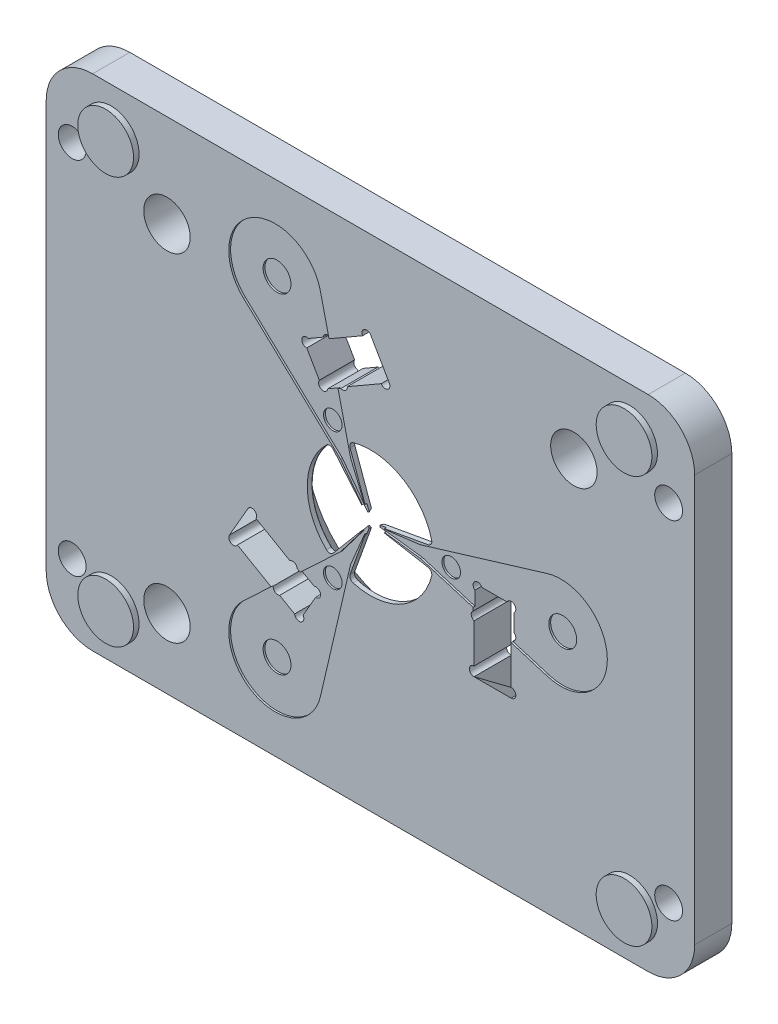
SolidWorks part; units mm, degrees
ref_plane "前基準面" through (0, 0, 0) normal (0, 0, 1) x (1, 0, 0)
ref_plane "上基準面" through (0, 0, 0) normal (0, 1, 0) x (1, 0, 0)
ref_plane "右基準面" through (0, 0, 0) normal (1, 0, 0) x (0, 0, -1)
sketch "草圖1" plane through (0, 0, 0) normal (0, 0, 1) x (1, 0, 0)
  line L1 (-38, 30) -> (38, 30)
  line L2 (-38, 30) -> (-38, -30)
  line L3 (-38, -30) -> (38, -30)
  line L4 (38, 30) -> (38, -30)
  line L5 (-38, 30) -> (38, -30) construction
  line L6 (-38, -30) -> (38, 30) construction
  point P0 (0, 0)
  point P28 (0, 0)
  dimension "D1" = 76
  dimension "D2" = 60
extrude "填料-伸長1" add sketch "草圖1" along normal blind 4
sketch "草圖2" plane through (0, 0, 4) normal (0, 0, 1) x (1, 0, 0)
  line L6 (0.3574, 0.005) -> (20.1903, 2.4807) construction
  line L7 (0.3574, -0.005) -> (20.1903, -2.4807) construction
  line L8 (0.3574, 0.005) -> (4.5094, 0.5233)
  line L9 (0.3574, -0.005) -> (4.5094, -0.5233)
  line L10 (6.1751, 0.8773) -> (19.0478, 4.7845)
  line L11 (6.1751, -0.8773) -> (19.0478, -4.7845)
  line L12 (-2.3278, -5.7864) -> (-5.3804, -18.8881)
  line L13 (-0.1744, -0.312) -> (-1.8015, -4.1669)
  line L14 (-0.183, -0.307) -> (-2.7079, -3.6436)
  line L15 (-3.8473, -4.9091) -> (-13.6674, -14.1037)
  line L16 (-3.8473, 4.9091) -> (-13.6674, 14.1037)
  line L17 (-0.183, 0.307) -> (-2.7079, 3.6436)
  line L18 (-0.1744, 0.312) -> (-1.8015, 4.1669)
  line L19 (-2.3278, 5.7864) -> (-5.3804, 18.8881)
  circle A7 centre (0, 0) radius 0.353 construction
  arc A8 (0.3574, 0.005) -> (0.3574, -0.005) centre (0.358, 0) ccw
  arc A9 (19.0478, -4.7845) -> (19.0478, 4.7845) centre (20.5, 0) ccw
  circle A10 centre (20.5, 0) radius 2.5 construction
  arc A11 (4.5094, -0.5233) -> (6.1751, -0.8773) centre (3.2707, -10.4463) cw
  arc A12 (4.5094, 0.5233) -> (6.1751, 0.8773) centre (3.2707, 10.4463) ccw
  arc A13 (-13.6674, -14.1037) -> (-5.3804, -18.8881) centre (-10.25, -17.7535) ccw
  arc A14 (-1.8015, -4.1669) -> (-2.3278, -5.7864) centre (7.4114, -8.0556) ccw
  arc A15 (-0.1744, -0.312) -> (-0.183, -0.307) centre (-0.179, -0.31) ccw
  arc A16 (-2.7079, -3.6436) -> (-3.8473, -4.9091) centre (-10.6821, 2.3906) cw
  arc A17 (-5.3804, 18.8881) -> (-13.6674, 14.1037) centre (-10.25, 17.7535) ccw
  arc A18 (-2.7079, 3.6436) -> (-3.8473, 4.9091) centre (-10.6821, -2.3906) ccw
  arc A19 (-0.183, 0.307) -> (-0.1744, 0.312) centre (-0.179, 0.31) ccw
  arc A20 (-1.8015, 4.1669) -> (-2.3278, 5.7864) centre (7.4114, 8.0556) cw
  point P17 (5.3574, -0.6291)
  point P20 (5.3574, 0.6291)
  point P46 (0, 0)
  dimension "D1" = 0.706
  dimension "D2" = 0.01
  dimension "D3" = 10
  dimension "D6" = 5
  dimension "D4" = 5
  dimension "D7" = 10
  dimension "D9" = 0.6201
  dimension "D5" = 20.5
  dimension "D8" = 3
extrude "除料-伸長1" cut sketch "草圖2" against normal blind 0.5
sketch "草圖5" plane through (0, 0, 4) normal (0, 0, 1) x (1, 0, 0)
  line L0 (-29.9, 26.9) -> (29.9, 26.9)
  line L1 (-38, 30) -> (-38, -30) construction
  line L2 (38, -30) -> (38, 30) construction
  line L3 (34.9, 21.9) -> (34.9, -21.9)
  line L4 (38, 30) -> (-38, 30) construction
  line L5 (-38, -30) -> (38, -30) construction
  line L6 (-29.9, -26.9) -> (29.9, -26.9)
  line L7 (-34.9, 21.9) -> (-34.9, -21.9)
  arc A0 (-29.9, -26.9) -> (-34.9, -21.9) centre (-29.9, -21.9) cw
  arc A1 (34.9, -21.9) -> (29.9, -26.9) centre (29.9, -21.9) cw
  arc A2 (29.9, 26.9) -> (34.9, 21.9) centre (29.9, 21.9) cw
  arc A3 (-34.9, 21.9) -> (-29.9, 26.9) centre (-29.9, 21.9) cw
  line M29 (38, -30) -> (38, 30)
  line M30 (38, 30) -> (-38, 30)
  line M31 (-38, 30) -> (-38, -30)
  line M32 (-38, -30) -> (38, -30)
  dimension "D5" = 5
  dimension "D1" = 3.1
  dimension "D2" = 3.1
  dimension "D3" = 3.1
  dimension "D4" = 3.1
extrude "除料-伸長4" cut sketch "草圖5" against normal blind 10 contours L7 A3 L0 A2 L3 A1 L6 A0 M32 M29 M30 M31 region at (0, -29.0317, 4)
ref_plane "平面1" through (0, 0, 4) normal (0, 0, 1) x (1, 0, 0)
sketch "草圖7" plane through (0, 0, 4) normal (0, 0, 1) x (1, 0, 0)
  line L0 (0, 0) -> (34.9, 0) construction
  line L1 (34.9, 21.9) -> (34.9, -21.9) construction
  line L2 (11.05, -0.2286) -> (15.25, -0.2286)
  line L3 (15.25, -0.2286) -> (15.25, -3.3286)
  line L4 (15.25, -3.3286) -> (11.05, -3.3286)
  line L5 (11.05, -3.3286) -> (11.05, -0.2286)
  line L6 (11.05, -1.7786) -> (15.25, -1.7786) construction
  line L7 (13.15, -0.2286) -> (13.15, -3.3286) construction
  line L8 (13.15, -1.7786) -> (11.05, -0.2286) construction
  line L9 (0, 0) -> (-12.75, -22.0836) construction
  line L10 (-6.575, -11.3882) -> (-6.9709, -11.1597) construction
  line L11 (-5.7229, -9.4553) -> (-7.8229, -13.0926)
  line L16 (-7.4271, 13.3212) -> (-5.3271, 9.6839)
  line L17 (-7.4271, 13.3212) -> (-4.7424, 14.8712)
  line L18 (-4.7424, 14.8712) -> (-2.6424, 11.2339)
  line L23 (13.15, -1.7786) -> (13.15, -13.7786) construction
  line L24 (11.15, -7.7786) -> (15.15, -7.7786)
  line L25 (11.15, -7.7786) -> (11.15, -8.7786)
  line L26 (11.15, -8.7786) -> (15.15, -8.7786)
  line L27 (15.15, -8.7786) -> (15.15, -7.7786)
  line L28 (-2.6424, 11.2339) -> (-5.3271, 9.6839)
  line L33 (-6.0847, 14.0962) -> (-3.9847, 10.4589) construction
  line L34 (11.15, -8.2786) -> (15.15, -8.2786) construction
  line L35 (-5.7229, -9.4553) -> (-8.4076, -7.9053)
  line L40 (-8.4076, -7.9053) -> (-10.5076, -11.5426)
  line L41 (0, 0) -> (-12.75, 22.0836) construction
  line L42 (-6.575, 11.3882) -> (-6.1791, 11.6168) construction
  line L43 (-6.3771, 11.5025) -> (-3.6924, 13.0525) construction
  line L44 (-10.5076, -11.5426) -> (-7.8229, -13.0926)
  line L45 (-7.0653, -8.6803) -> (-9.1653, -12.3176) construction
  line L46 (-9.4576, -9.7239) -> (-6.7729, -11.2739) construction
  line L47 (-8.4076, -7.9053) -> (-7.8229, -13.0926) construction
  line L48 (-10.5076, -11.5426) -> (-5.7229, -9.4553) construction
  line L49 (-9.4576, -9.7239) -> (-17.1653, -5.2739) construction
  line L50 (-12.3114, -5.7669) -> (-14.3114, -9.231)
  line L51 (-4.7424, 14.8712) -> (-5.3271, 9.6839) construction
  line L52 (-7.4271, 13.3212) -> (-2.6424, 11.2339) construction
  line L53 (-3.6924, 13.0525) -> (4.0153, 17.5025) construction
  line L54 (-0.8386, 17.0096) -> (1.1614, 13.5455)
  line L55 (-0.8386, 17.0096) -> (0.0275, 17.5096)
  line L56 (0.0275, 17.5096) -> (2.0275, 14.0455)
  line L57 (2.0275, 14.0455) -> (1.1614, 13.5455)
  line L58 (-0.4055, 17.2596) -> (1.5945, 13.7955) construction
  line L59 (-4.3091, 13.6779) -> (-3.8841, 12.9418) construction
  line L60 (-4.7841, 14.5007) -> (-4.3091, 13.6779) construction
  line L61 (-12.3114, -5.7669) -> (-13.1775, -5.2669)
  line L62 (-13.1775, -5.2669) -> (-15.1775, -8.731)
  line L63 (-15.1775, -8.731) -> (-14.3114, -9.231)
  line L64 (-12.7445, -5.5169) -> (-14.7445, -8.981) construction
  line L65 (-10.1659, -11.3935) -> (-9.6909, -10.5708) construction
  line L66 (-9.6909, -10.5708) -> (-9.2659, -9.8347) construction
  circle A0 centre (11.35, -0.45) radius 0.5
  circle A1 centre (14.95, -0.45) radius 0.5
  circle A2 centre (14.95, -3.1071) radius 0.5
  circle A3 centre (11.35, -3.1071) radius 0.5
  circle A4 centre (13.15, -0.9886) radius 0.15 construction
  arc A11 (-13.6674, -14.1037) -> (-5.3804, -18.8881) centre (-10.25, -17.7535) ccw construction
  circle A17 centre (-7.0853, 13.1721) radius 0.5
  circle A20 centre (15.15, -8.2786) radius 0.5
  circle A21 centre (11.15, -8.2786) radius 0.5
  arc A24 (-5.3804, 18.8881) -> (-13.6674, 14.1037) centre (-10.25, 17.7535) ccw construction
  circle A25 centre (-7.8647, -12.7221) radius 0.5
  circle A26 centre (-10.1659, -11.3935) radius 0.5
  circle A27 centre (-6.0647, -9.6044) radius 0.5
  circle A28 centre (-8.3659, -8.2758) radius 0.5
  circle A29 centre (-14.7445, -8.981) radius 0.5
  circle A30 centre (-12.7445, -5.5169) radius 0.5
  circle A31 centre (-4.7841, 14.5007) radius 0.5
  circle A32 centre (-2.9841, 11.383) radius 0.5
  circle A33 centre (-5.2853, 10.0544) radius 0.5
  circle A34 centre (-0.4055, 17.2596) radius 0.5
  circle A35 centre (1.5945, 13.7955) radius 0.5
  point P24 (13.15, -7.7786)
  point P37 (-6.7729, -11.2739)
  point P52 (-6.3771, 11.5025)
  point P70 (0.1614, 15.2775)
  point P89 (-13.3114, -7.4989)
  dimension "D3" = 1
  dimension "D4" = 0.3
  dimension "D10" = 13.15
  dimension "D23" = 0.3
  dimension "D17" = 1
  dimension "D24" = 0.45
  dimension "D25" = 4
  dimension "D30" = 0.45
  dimension "D20" = 1
  dimension "D1" = 4.2
  dimension "D2" = 3.1
  dimension "D5" = 0.79
  dimension "D6" = 0.45
  dimension "D7" = 13.15
  dimension "D11" = 13.15
  dimension "D12" = 4.2
  dimension "D13" = 4
  dimension "D14" = 1
  dimension "D15" = 4.2
  dimension "D16" = 3.1
  dimension "D18" = 4.95
  dimension "D19" = 3.1
  dimension "D21" = 0.3
  dimension "D22" = 0.3
  dimension "D26" = 1
  dimension "D27" = 4.95
  dimension "D29" = 1.25
  dimension "D31" = 4
  dimension "D32" = 1
  dimension "D33" = 4.95
  dimension "D35" = 1.25
extrude "除料-伸長5" cut sketch "草圖7" against normal through all contours A2 L3 A1 L2 A0 L5 A3 L4 | A25 A27 | A17 L17 | A35 L56 A34 L54 | A28 L40 A26 L44 A25 L11 A27 L35 | A30 L62 A29 L50 | A2 | A1 | A0 | A3 | A27 | A25 | A17 | L24 L27 L26 L25 | A20 | A21 | A33 | A32 | A31 | A34 | A35 | A26 | A28 | A29 | A30 region at (13.15, -1.7786, 4) region at (-6.1957, -9.613, 4) region at (-8.1153, -10.4989, 4) region at (-5.0347, 12.2775, 4) region at (-13.7445, -7.2489, 4) region at (0.5945, 15.5275, 4)
sketch "草圖9" plane through (0, 0, 4) normal (0, 0, 1) x (1, 0, 0)
  line L0 (34.9, 21.9) -> (24.9, 21.9) construction
  line L1 (24.9, 21.9) -> (24.9, -21.9) construction
  line L2 (24.9, -21.9) -> (34.9, -21.9) construction
  line L3 (34.9, 21.9) -> (34.9, -21.9) construction
  line L4 (0, 26.9) -> (0, -26.9) construction
  line L5 (-29.9, 26.9) -> (29.9, 26.9) construction
  line L6 (-29.9, -26.9) -> (29.9, -26.9) construction
  line L7 (34.9, 0) -> (-34.9, 0) construction
  line L8 (-34.9, 21.9) -> (-34.9, -21.9) construction
  circle A0 centre (32.1, 17.9) radius 1.5
  circle A3 centre (-32.1, 19.4) radius 1.5
  circle A4 centre (-32.1, -19.4) radius 1.5
  circle A5 centre (32.1, -19.4) radius 1.5
  dimension "D2" = 3
  dimension "D5" = 2.8
  dimension "D3" = 3
  dimension "D7" = 2.8
  dimension "D1" = 10
  dimension "D4" = 4
  dimension "D6" = 2.5
extrude "除料-伸長6" cut sketch "草圖9" against normal through all
sketch "草圖13" plane through (0, 0, 4) normal (0, 0, 1) x (1, 0, 0)
  line L0 (5.358, 0.6292) -> (19.0478, 4.7845) construction
  line L1 (0.3574, 0.005) -> (20.1903, 2.4807) construction
  line L2 (20.1903, -2.4807) -> (0.3574, -0.005) construction
  line L15 (0.3574, 0.005) -> (5.358, 0.6292) construction
  line L16 (0.3574, -0.005) -> (5.358, -0.6292) construction
  line L17 (5.358, -0.6292) -> (19.0478, -4.7845) construction
  line L18 (-2.1341, -4.9548) -> (-5.3804, -18.8881) construction
  line L19 (-0.1744, -0.312) -> (-2.1341, -4.9548) construction
  line L20 (-0.183, -0.307) -> (-3.2239, -4.3256) construction
  line L21 (-3.2239, -4.3256) -> (-13.6673, -14.1036) construction
  line L22 (-3.2239, 4.3256) -> (-13.6673, 14.1036) construction
  line L23 (-0.183, 0.307) -> (-3.2239, 4.3256) construction
  line L24 (-0.1744, 0.312) -> (-2.1341, 4.9548) construction
  line L25 (-2.1341, 4.9548) -> (-5.3804, 18.8881) construction
  line L41 (0.3574, 0.005) -> (6.1962, 1.0512)
  line L42 (0.3574, -0.005) -> (6.1962, -1.0512)
  line L43 (-0.183, -0.307) -> (-4.0085, -4.8405)
  line L44 (-0.1744, -0.312) -> (-2.1877, -5.8917)
  line L45 (-0.1744, 0.312) -> (-2.1877, 5.8917)
  line L46 (-0.183, 0.307) -> (-4.0085, 4.8405)
  circle A8 centre (0, 0) radius 0.353 construction
  arc A9 (0.3574, 0.005) -> (0.3574, -0.005) centre (0.358, 0) ccw construction
  circle A10 centre (20.5, 0) radius 2.5 construction
  arc A11 (19.0478, -4.7845) -> (19.0478, 4.7845) centre (20.5, 0) ccw construction
  arc A12 (-13.6673, -14.1036) -> (-5.3804, -18.8881) centre (-10.25, -17.7535) ccw construction
  arc A13 (-0.1744, -0.312) -> (-0.183, -0.307) centre (-0.179, -0.31) ccw construction
  arc A14 (-5.3804, 18.8881) -> (-13.6673, 14.1036) centre (-10.25, 17.7535) ccw construction
  arc A15 (-0.183, 0.307) -> (-0.1744, 0.312) centre (-0.179, 0.31) ccw construction
  arc A16 (-4.7391, 4.8766) -> (-4.7391, -4.8766) centre (0, 0) ccw
  arc A17 (-0.183, 0.307) -> (-0.1744, 0.312) centre (-0.179, 0.31) ccw
  arc A18 (-0.1744, -0.312) -> (-0.183, -0.307) centre (-0.179, -0.31) ccw
  arc A19 (-1.8537, -6.5425) -> (6.5928, -1.6658) centre (0, 0) ccw
  arc A20 (0.3574, 0.005) -> (0.3574, -0.005) centre (0.358, 0) ccw
  arc A21 (6.5928, 1.6658) -> (-1.8537, 6.5425) centre (0, 0) ccw
  arc A22 (6.1962, -1.0512) -> (6.5928, -1.6658) centre (6.108, -1.5434) cw
  arc A23 (6.1962, 1.0512) -> (6.5928, 1.6658) centre (6.108, 1.5434) ccw
  arc A24 (-2.1877, 5.8917) -> (-1.8537, 6.5425) centre (-1.7174, 6.0614) cw
  arc A25 (-4.0085, 4.8405) -> (-4.7391, 4.8766) centre (-4.3906, 4.518) ccw
  arc A26 (-4.0085, -4.8405) -> (-4.7391, -4.8766) centre (-4.3906, -4.518) cw
  arc A27 (-2.1877, -5.8917) -> (-1.8537, -6.5425) centre (-1.7174, -6.0614) ccw
  point P31 (0, 0)
  point P38 (6.7034, -1.1421)
  point P41 (6.7034, 1.1421)
  point P49 (0, 0)
  dimension "D1" = 0.706
  dimension "D2" = 0.01
  dimension "D3" = 5
  dimension "D6" = 5
  dimension "D5" = 10
  dimension "D8" = 13.6
  dimension "D12" = 0.5
  dimension "D13" = 0.5
  dimension "D4" = 20.5
  dimension "D9" = 0.1
  dimension "D10" = 0.1
  dimension "D11" = 3
  dimension "D7" = 3
extrude "除料-伸長8" cut sketch "草圖13" against normal blind 0.5
sketch "草圖12" plane through (0, 0, 3.5) normal (0, 0, 1) x (1, 0, 0)
  line L0 (11.05, -2.357) -> (11.05, -0.85) construction
  line L1 (11.7983, -0.2286) -> (14.5017, -0.2286) construction
  line L2 (15.25, -0.85) -> (15.25, -2.7071) construction
  line L3 (15.0966, -3.5852) -> (19.0478, -4.7845) construction
  line L4 (19.0478, 4.7845) -> (6.1751, 0.8773) construction
  line L5 (4.5094, 0.5233) -> (0.3574, 0.005) construction
  line L6 (0.3574, -0.005) -> (4.5094, -0.5233) construction
  line L7 (6.1751, -0.8773) -> (11.05, -2.357) construction
  line L8 (-10.6531, -11.2814) -> (-13.6674, -14.1037) construction
  line L9 (-5.3804, -18.8881) -> (-2.3278, -5.7864) construction
  line L10 (-1.8015, -4.1669) -> (-0.1744, -0.312) construction
  line L11 (-0.183, -0.307) -> (-2.7079, -3.6436) construction
  line L12 (-3.8473, -4.9091) -> (-7.5662, -8.3911) construction
  line L13 (-7.5662, -8.3911) -> (-6.2611, -9.1446) construction
  line L14 (-6.0971, -10.1033) -> (-7.4488, -12.4446) construction
  line L15 (-8.3611, -12.7819) -> (-9.9695, -11.8533) construction
  line L16 (-3.4838, 10.7481) -> (-4.7889, 9.9946) construction
  line L17 (-5.7012, 10.3319) -> (-7.0529, 12.6731) construction
  line L18 (-6.8889, 13.6319) -> (-5.2805, 14.5605) construction
  line L19 (-4.4434, 14.8666) -> (-5.3804, 18.8881) construction
  line L20 (-13.6674, 14.1037) -> (-3.8473, 4.9091) construction
  line L21 (-2.7079, 3.6436) -> (-0.183, 0.307) construction
  line L22 (-0.1744, 0.312) -> (-1.8015, 4.1669) construction
  line L23 (-2.3278, 5.7864) -> (-3.4838, 10.7481) construction
  line L24 (11.05, -2.357) -> (11.05, -0.85)
  line L25 (11.7983, -0.2286) -> (14.5017, -0.2286)
  line L26 (15.25, -0.85) -> (15.25, -2.7071)
  line L27 (15.0966, -3.5852) -> (19.0478, -4.7845)
  line L28 (19.0478, 4.7845) -> (6.1751, 0.8773)
  line L29 (4.5094, 0.5233) -> (0.3574, 0.005)
  line L30 (0.3574, -0.005) -> (4.5094, -0.5233)
  line L31 (6.1751, -0.8773) -> (11.05, -2.357)
  line L32 (-10.6531, -11.2814) -> (-13.6674, -14.1037)
  line L33 (-5.3804, -18.8881) -> (-2.3278, -5.7864)
  line L34 (-1.8015, -4.1669) -> (-0.1744, -0.312)
  line L35 (-0.183, -0.307) -> (-2.7079, -3.6436)
  line L36 (-3.8473, -4.9091) -> (-7.5662, -8.3911)
  line L37 (-7.5662, -8.3911) -> (-6.2611, -9.1446)
  line L38 (-6.0971, -10.1033) -> (-7.4488, -12.4446)
  line L39 (-8.3611, -12.7819) -> (-9.9695, -11.8533)
  line L40 (-3.4838, 10.7481) -> (-4.7889, 9.9946)
  line L41 (-5.7012, 10.3319) -> (-7.0529, 12.6731)
  line L42 (-6.8889, 13.6319) -> (-5.2805, 14.5605)
  line L43 (-4.4434, 14.8666) -> (-5.3804, 18.8881)
  line L44 (-13.6674, 14.1037) -> (-3.8473, 4.9091)
  line L45 (-2.7079, 3.6436) -> (-0.183, 0.307)
  line L46 (-0.1744, 0.312) -> (-1.8015, 4.1669)
  line L47 (-2.3278, 5.7864) -> (-3.4838, 10.7481)
  arc A0 (11.7983, -0.2286) -> (11.05, -0.85) centre (11.35, -0.45) ccw construction
  arc A1 (15.25, -0.85) -> (14.5017, -0.2286) centre (14.95, -0.45) ccw construction
  arc A2 (15.0966, -3.5852) -> (15.25, -2.7071) centre (14.95, -3.1071) ccw construction
  arc A3 (19.0478, -4.7845) -> (19.0478, 4.7845) centre (20.5, 0) ccw construction
  arc A4 (4.5094, 0.5233) -> (6.1751, 0.8773) centre (3.2707, 10.4463) ccw construction
  arc A6 (6.1751, -0.8773) -> (4.5094, -0.5233) centre (3.2707, -10.4463) ccw construction
  arc A7 (-10.6531, -11.2814) -> (-9.9695, -11.8533) centre (-10.1659, -11.3935) ccw construction
  arc A8 (-13.6674, -14.1037) -> (-5.3804, -18.8881) centre (-10.25, -17.7535) ccw construction
  arc A9 (-1.8015, -4.1669) -> (-2.3278, -5.7864) centre (7.4114, -8.0556) ccw construction
  arc A11 (-3.8473, -4.9091) -> (-2.7079, -3.6436) centre (-10.6821, 2.3906) ccw construction
  arc A12 (-6.0971, -10.1033) -> (-6.2611, -9.1446) centre (-6.0647, -9.6044) ccw construction
  arc A13 (-8.3611, -12.7819) -> (-7.4488, -12.4446) centre (-7.8647, -12.7221) ccw construction
  arc A14 (-5.7012, 10.3319) -> (-4.7889, 9.9946) centre (-5.2853, 10.0544) ccw construction
  arc A15 (-6.8889, 13.6319) -> (-7.0529, 12.6731) centre (-7.0853, 13.1721) ccw construction
  arc A16 (-4.4434, 14.8666) -> (-5.2805, 14.5605) centre (-4.7841, 14.5007) ccw construction
  arc A17 (-5.3804, 18.8881) -> (-13.6674, 14.1037) centre (-10.25, 17.7535) ccw construction
  arc A18 (-2.7079, 3.6436) -> (-3.8473, 4.9091) centre (-10.6821, -2.3906) ccw construction
  arc A20 (-2.3278, 5.7864) -> (-1.8015, 4.1669) centre (7.4114, 8.0556) ccw construction
  arc A21 (11.7983, -0.2286) -> (11.05, -0.85) centre (11.35, -0.45) ccw
  arc A22 (15.25, -0.85) -> (14.5017, -0.2286) centre (14.95, -0.45) ccw
  arc A23 (15.0966, -3.5852) -> (15.25, -2.7071) centre (14.95, -3.1071) ccw
  arc A24 (19.0478, -4.7845) -> (19.0478, 4.7845) centre (20.5, 0) ccw
  arc A25 (4.5094, 0.5233) -> (6.1751, 0.8773) centre (3.2707, 10.4463) ccw
  arc A26 (0.3574, 0.005) -> (0.3574, -0.005) centre (0.358, 0) ccw
  arc A27 (6.1751, -0.8773) -> (4.5094, -0.5233) centre (3.2707, -10.4463) ccw
  arc A28 (-10.6531, -11.2814) -> (-9.9695, -11.8533) centre (-10.1659, -11.3935) ccw
  arc A29 (-13.6674, -14.1037) -> (-5.3804, -18.8881) centre (-10.25, -17.7535) ccw
  arc A30 (-1.8015, -4.1669) -> (-2.3278, -5.7864) centre (7.4114, -8.0556) ccw
  arc A31 (-0.1744, -0.312) -> (-0.183, -0.307) centre (-0.179, -0.31) ccw
  arc A32 (-3.8473, -4.9091) -> (-2.7079, -3.6436) centre (-10.6821, 2.3906) ccw
  arc A33 (-6.0971, -10.1033) -> (-6.2611, -9.1446) centre (-6.0647, -9.6044) ccw
  arc A34 (-8.3611, -12.7819) -> (-7.4488, -12.4446) centre (-7.8647, -12.7221) ccw
  arc A35 (-5.7012, 10.3319) -> (-4.7889, 9.9946) centre (-5.2853, 10.0544) ccw
  arc A36 (-6.8889, 13.6319) -> (-7.0529, 12.6731) centre (-7.0853, 13.1721) ccw
  arc A37 (-4.4434, 14.8666) -> (-5.2805, 14.5605) centre (-4.7841, 14.5007) ccw
  arc A38 (-5.3804, 18.8881) -> (-13.6674, 14.1037) centre (-10.25, 17.7535) ccw
  arc A39 (-2.7079, 3.6436) -> (-3.8473, 4.9091) centre (-10.6821, -2.3906) ccw
  arc A40 (-0.183, 0.307) -> (-0.1744, 0.312) centre (-0.179, 0.31) ccw
  arc A41 (-2.3278, 5.7864) -> (-1.8015, 4.1669) centre (7.4114, 8.0556) ccw
  circle A42 centre (0, 0) radius 0.353 construction
  dimension "D1" = 0.005
extrude "填料-伸長2" add sketch "草圖12" along normal blind 0.5
sketch "草圖15" plane through (0, 0, 0) normal (0, 1, 0) x (1, 0, 0)
  line L0 (0.0275, 0) -> (0.0275, -4.5737) construction
  line L7 (-29.9, 0) -> (29.9, 0) construction
  line L8 (11.0275, 0) -> (0.0275, 0)
  line L10 (0.0275, -3.5) -> (6.8275, -3.5)
  line L11 (-1.8537, -3.5) -> (6.5928, -3.5) construction
  line L12 (6.8275, -3.5) -> (11.0275, 0)
  line L13 (0.0275, -3.5) -> (0.0275, 0)
  dimension "D1" = 6.8
  dimension "D2" = 11
revolve "除料-旋轉2" cut sketch "草圖15" angle 360 about L0
sketch "草圖16" plane through (0, 0, 0) normal (0, 1, 0) x (1, 0, 0)
  line L0 (0, 0) -> (0, -4.8454) construction
  line L1 (0.353, -4.18) -> (0.353, -3.5)
  line L2 (6.8275, -3.5) -> (0.0137, -3.5) construction
  line L3 (0.353, -3.5) -> (0.7456, -3.5)
  line L4 (0.7456, -3.5) -> (0.353, -4.18)
  line L5 (-29.59, -4) -> (29.59, -4) construction
  dimension "D1" = 0.353
  dimension "D2" = 30
  dimension "D3" = 0.18
revolve "除料-旋轉3" cut sketch "草圖16" angle 360 about L0
sketch "草圖17" plane through (0, 0, 4) normal (0, 0, 1) x (1, 0, 0)
  line L0 (-29.9, 26.9) -> (29.9, 26.9) construction
  line L1 (-34.9, 21.9) -> (-34.9, -21.9) construction
  line L2 (0, 26.9) -> (0, -26.9) construction
  line L3 (-29.9, -26.9) -> (29.9, -26.9) construction
  circle A0 centre (-21.9, 16.9) radius 2.5
  circle A1 centre (21.9, 16.9) radius 2.5
  circle A2 centre (-21.9, -19.4) radius 2.5
  dimension "D3" = 5
  dimension "D4" = 5
  dimension "D1" = 10
  dimension "D2" = 13
  dimension "D5" = 7.5
extrude "除料-伸長9" cut sketch "草圖17" against normal through all
sketch "草圖18" plane through (0, 0, 4) normal (0, 0, 1) x (1, 0, 0)
  line L0 (13.15, -0.2286) -> (13.15, -8.7786) construction
  line L1 (11.7983, -0.2286) -> (14.5017, -0.2286) construction
  line L2 (11.15, -8.7786) -> (15.15, -8.7786) construction
  line L3 (14.2511, -3.3286) -> (11.7983, -3.3286) construction
  line L4 (11.15, -3.3286) -> (15.15, -3.3286)
  line L5 (11.15, -3.3286) -> (11.15, -7.7786)
  line L6 (11.15, -7.7786) -> (15.15, -7.7786)
  line L7 (15.15, -3.3286) -> (15.15, -7.7786)
  line L8 (11.15, -3.3286) -> (15.15, -7.7786) construction
  line L9 (11.15, -7.7786) -> (15.15, -3.3286) construction
  line L10 (-6.3771, 11.5025) -> (1.0275, 15.7775) construction
  line L11 (-5.7012, 10.3319) -> (-7.0529, 12.6731) construction
  line L12 (0.0275, 17.5096) -> (2.0275, 14.0455) construction
  line L13 (-0.8386, 17.0096) -> (1.1614, 13.5455) construction
  line L14 (-0.8386, 17.0096) -> (1.1614, 13.5455)
  line L15 (-0.8386, 17.0096) -> (-4.6924, 14.7846)
  line L16 (-4.6924, 14.7846) -> (-2.6924, 11.3205)
  line L17 (1.1614, 13.5455) -> (-2.6924, 11.3205)
  line L18 (-0.8386, 17.0096) -> (-2.6924, 11.3205) construction
  line L19 (-4.6924, 14.7846) -> (1.1614, 13.5455) construction
  line L20 (-4.2429, 14.0061) -> (-3.0165, 11.8819) construction
  line L21 (-6.7729, -11.2739) -> (-14.1775, -6.9989) construction
  line L22 (-6.0971, -10.1033) -> (-7.4488, -12.4446) construction
  line L23 (-13.1775, -5.2669) -> (-15.1775, -8.731) construction
  line L24 (-12.3114, -5.7669) -> (-14.3114, -9.231) construction
  line L25 (-10.4576, -11.456) -> (-8.4576, -7.9919)
  line L26 (-10.4576, -11.456) -> (-14.3114, -9.231)
  line L27 (-14.3114, -9.231) -> (-12.3114, -5.7669)
  line L28 (-8.4576, -7.9919) -> (-12.3114, -5.7669)
  line L29 (-10.4576, -11.456) -> (-12.3114, -5.7669) construction
  line L30 (-14.3114, -9.231) -> (-8.4576, -7.9919) construction
  line L31 (-8.7818, -8.5533) -> (-10.0082, -10.6776) construction
  point P6 (13.15, -5.5536)
  point P20 (-1.7655, 14.165)
  point P29 (-11.3845, -8.6114)
extrude "除料-伸長10" cut sketch "草圖18" against normal blind 0.9
sketch "草圖20" plane through (0, 0, 4) normal (0, 0, 1) x (1, 0, 0)
  line L0 (20.1903, 2.4807) -> (0.3574, 0.005) construction
  line L1 (0.3574, -0.005) -> (20.1903, -2.4807) construction
  line L2 (0.3574, 0.005) -> (5.358, 0.6292)
  line L3 (0.3574, -0.005) -> (5.358, -0.6292)
  line L4 (5.358, 0.6292) -> (19.0478, 4.7845)
  line L5 (5.358, -0.6292) -> (19.0478, -4.7845)
  line L6 (-0.183, -0.307) -> (-3.2239, -4.3256)
  line L7 (-3.2239, -4.3256) -> (-13.6673, -14.1036)
  line L8 (-2.1341, -4.9548) -> (-5.3804, -18.8881)
  line L9 (-0.1744, -0.312) -> (-2.1341, -4.9548)
  line L10 (-7.9468, -18.7257) -> (-0.1744, -0.312) construction
  line L11 (-0.183, -0.307) -> (-12.2436, -16.245) construction
  line L12 (-0.1744, 0.312) -> (-2.1341, 4.9548)
  line L13 (-2.1341, 4.9548) -> (-5.3804, 18.8881)
  line L14 (-3.2239, 4.3256) -> (-13.6673, 14.1036)
  line L15 (-0.183, 0.307) -> (-3.2239, 4.3256)
  line L16 (-12.2436, 16.245) -> (-0.183, 0.307) construction
  line L17 (-0.1744, 0.312) -> (-7.9468, 18.7257) construction
  circle A0 centre (0, 0) radius 0.353 construction
  arc A1 (0.3574, 0.005) -> (0.3574, -0.005) centre (0.358, 0) ccw
  circle A2 centre (20.5, 0) radius 2.5 construction
  arc A3 (19.0478, -4.7845) -> (19.0478, 4.7845) centre (20.5, 0) ccw
  arc A4 (-0.1744, -0.312) -> (-0.183, -0.307) centre (-0.179, -0.31) ccw
  arc A5 (-13.6673, -14.1036) -> (-5.3804, -18.8881) centre (-10.25, -17.7535) ccw
  circle A6 centre (-10.25, -17.7535) radius 2.5 construction
  arc A7 (-0.183, 0.307) -> (-0.1744, 0.312) centre (-0.179, 0.31) ccw
  arc A8 (-5.3804, 18.8881) -> (-13.6673, 14.1036) centre (-10.25, 17.7535) ccw
  circle A9 centre (-10.25, 17.7535) radius 2.5 construction
  point P38 (0, 0)
  dimension "D1" = 0.706
  dimension "D2" = 0.01
  dimension "D3" = 5
  dimension "D5" = 10
  dimension "D4" = 20.5
  dimension "D6" = 5
  dimension "D7" = 3
extrude "除料-伸長11" cut sketch "草圖20" against normal blind 0.2
sketch "草圖21" plane through (0, 0, 0) normal (0, 1, 0) x (1, 0, 0)
  line L0 (0, 0) -> (0, -4.6448) construction
  line L1 (0.353, 0) -> (0.353, -4.25)
  line L2 (10.998, 0) -> (-5.5861, 0) construction
  line L3 (0.353, -4.25) -> (0.553, -4.25)
  line L4 (0.553, -4.25) -> (3.0067, 0)
  line L5 (3.0067, 0) -> (0.353, 0)
  line L6 (0.4566, -4) -> (5.358, -4) construction
  dimension "D1" = 0.706
  dimension "D2" = 0.2
  dimension "D3" = 0.25
  dimension "D4" = 30
revolve "除料-旋轉4" cut sketch "草圖21" angle 360 about L0
ref_plane "平面2" through (11.15, 0, 0) normal (1, 0, 0) x (0, 0, -1)
sketch "草圖22" plane through (11.15, 0, 0) normal (1, 0, 0) x (0, 0, -1)
  line L1 (-4, -8.7786) -> (0, -8.7786)
  line L3 (0, -8.7786) -> (0, -11.7786)
  line L10 (0, -10.1033) -> (0, -12.4446) construction
  line L11 (0, -11.7786) -> (-4, -8.7786)
  line L13 (0, -7.7786) -> (-3.1, -7.7786)
  line L14 (-3.1, -7.7786) -> (-4, -7.7786)
  line L15 (-4, -7.7786) -> (-4, -8.7786)
  line L16 (-4, -8.7786) -> (0, -8.7786)
  line L17 (0, -8.7786) -> (0, -7.7786)
  line L18 (0, -7.7786) -> (-3.1, -7.7786) construction
  line L19 (-3.1, -7.7786) -> (-4, -7.7786) construction
  line L20 (-4, -7.7786) -> (-4, -8.7786) construction
  line L21 (-4, -8.7786) -> (0, -8.7786) construction
  line L22 (0, -8.7786) -> (0, -7.7786) construction
  dimension "D1" = 0
  dimension "D2" = 3
extrude "除料-伸長12" cut sketch "草圖22" along normal blind 4
ref_plane "平面3" through (-5.575, -9.6562, 0) normal (-0.5, -0.866, 0) x (-0.866, 0.5, 0)
sketch "草圖23" plane through (-5.575, -9.6562, 0) normal (-0.5, -0.866, 0) x (-0.866, 0.5, 0)
  line L1 (8.7786, -4) -> (8.7786, 0)
  line L2 (8.7786, 0) -> (11.7786, 0)
  line L11 (39.3442, 0) -> (-12.4442, 0) construction
  line L12 (11.7786, 0) -> (8.7786, -4)
  line L14 (7.7786, 0) -> (7.7786, -3.1)
  line L15 (7.7786, -3.1) -> (7.7786, -4)
  line L16 (7.7786, -4) -> (8.7786, -4)
  line L17 (8.7786, -4) -> (8.7786, 0)
  line L18 (8.7786, 0) -> (7.7786, 0)
  line L19 (7.7786, 0) -> (7.7786, -3.1) construction
  line L20 (7.7786, -3.1) -> (7.7786, -4) construction
  line L21 (7.7786, -4) -> (8.7786, -4) construction
  line L22 (8.7786, -4) -> (8.7786, 0) construction
  line L23 (8.7786, 0) -> (7.7786, 0) construction
  dimension "D1" = 0
  dimension "D2" = 3
extrude "除料-伸長13" cut sketch "草圖23" along normal blind 4
ref_plane "平面4" through (-7.575, 13.1203, 0) normal (0.5, -0.866, 0) x (-0.866, -0.5, 0)
sketch "草圖24" plane through (-7.575, 13.1203, 0) normal (0.5, -0.866, 0) x (-0.866, -0.5, 0)
  line L5 (-8.7786, -4) -> (-8.7786, 0)
  line L6 (-8.7786, 0) -> (-11.7786, 0)
  line L7 (12.4442, 0) -> (-39.3442, 0) construction
  line L8 (-11.7786, 0) -> (-8.7786, -4)
  line L10 (-7.7786, 0) -> (-8.7786, 0)
  line L11 (-8.7786, 0) -> (-8.7786, -4)
  line L12 (-8.7786, -4) -> (-7.7786, -4)
  line L13 (-7.7786, -4) -> (-7.7786, -3.1)
  line L14 (-7.7786, -3.1) -> (-7.7786, 0)
  line L15 (-7.7786, 0) -> (-8.7786, 0) construction
  line L16 (-8.7786, 0) -> (-8.7786, -4) construction
  line L17 (-8.7786, -4) -> (-7.7786, -4) construction
  line L18 (-7.7786, -4) -> (-7.7786, -3.1) construction
  line L19 (-7.7786, -3.1) -> (-7.7786, 0) construction
  dimension "D1" = 0
  dimension "D2" = 3
extrude "除料-伸長14" cut sketch "草圖24" along normal blind 4
ref_plane "平面5" through (0, 0, 4) normal (0, 0, 1) x (1, 0, 0)
sketch "草圖26" plane through (0, 0, 4) normal (0, 0, 1) x (1, 0, 0)
  line L0 (0, 0) -> (34.9, 0) construction
  line L5 (34.9, 21.9) -> (34.9, -21.9) construction
  line L6 (1.5193, 0) -> (1.5193, 0.15) construction
  line L7 (5.358, 0.6292) -> (0.6957, 0.0472) construction
  circle A0 centre (0, 0) radius 1.5266
  dimension "D1" = 0.15
extrude "除料-伸長15" cut sketch "草圖26" against normal blind 0.2
ref_plane "平面6" through (0, 0, 3.8) normal (0, 0, 1) x (1, 0, 0)
sketch "草圖27" plane through (0, 0, 3.8) normal (0, 0, 1) x (1, 0, 0)
  line L0 (0, 0) -> (34.9, 0) construction
  line L1 (34.9, 21.9) -> (34.9, -21.9) construction
  circle A0 centre (20.5, 0) radius 1.5
  circle A1 centre (8.5, 0) radius 1
  circle A2 centre (-4.25, -7.3612) radius 1
  circle A3 centre (-10.25, -17.7535) radius 1.5
  circle A4 centre (-4.25, 7.3612) radius 1
  circle A5 centre (-10.25, 17.7535) radius 1.5
  point P20 (0, 0)
  dimension "D1" = 3
  dimension "D2" = 2
  dimension "D3" = 8.5
  dimension "D4" = 3
extrude "除料-伸長16" cut sketch "草圖27" against normal blind 0.2
sketch "草圖29" plane through (0, 0, 4) normal (0, 0, 1) x (1, 0, 0)
  line L0 (0, 26.9) -> (0, -26.9) construction
  line L1 (-29.9, 26.9) -> (29.9, 26.9) construction
  line L2 (-29.9, -26.9) -> (29.9, -26.9) construction
  line L3 (-34.9, 0) -> (34.9, 0) construction
  line L4 (-34.9, 21.9) -> (-34.9, -21.9) construction
  line L5 (34.9, 21.9) -> (34.9, -21.9) construction
  circle A0 centre (-27.9, 21.9) radius 3
  circle A1 centre (27.9, 21.9) radius 3
  circle A2 centre (27.9, -21.9) radius 3
  circle A3 centre (-27.9, -21.9) radius 3
  dimension "D1" = 6
  dimension "D2" = 5
  dimension "D3" = 7
extrude "填料-伸長3" add sketch "草圖29" along normal blind 0.6
sketch "草圖30" plane through (0, 0, 3.1) normal (0, 0, 1) x (1, 0, 0)
  line L4 (-4.3682, 14.2231) -> (-3.0165, 11.8819)
  line L5 (-2.4873, 11.4389) -> (1.1614, 13.5455)
  line L6 (1.1614, 13.5455) -> (-0.8386, 17.0096)
  line L7 (-0.8386, 17.0096) -> (-4.4873, 14.903)
  line L8 (-4.3682, 14.2231) -> (-3.0165, 11.8819)
  line L9 (-2.4873, 11.4389) -> (1.1614, 13.5455)
  line L10 (1.1614, 13.5455) -> (-0.8386, 17.0096)
  line L11 (-0.8386, 17.0096) -> (-4.4873, 14.903)
  line L12 (-10.1335, -10.8946) -> (-8.7818, -8.5533)
  line L13 (-8.6627, -7.8735) -> (-12.3114, -5.7669)
  line L14 (-12.3114, -5.7669) -> (-14.3114, -9.231)
  line L15 (-14.3114, -9.231) -> (-10.6627, -11.3376)
  line L16 (-10.1335, -10.8946) -> (-8.7818, -8.5533)
  line L17 (-8.6627, -7.8735) -> (-12.3114, -5.7669)
  line L18 (-12.3114, -5.7669) -> (-14.3114, -9.231)
  line L19 (-14.3114, -9.231) -> (-10.6627, -11.3376)
  line L20 (14.5017, -3.3286) -> (11.7983, -3.3286)
  line L21 (11.15, -3.5654) -> (11.15, -7.7786)
  line L22 (11.15, -7.7786) -> (15.15, -7.7786)
  line L23 (15.15, -7.7786) -> (15.15, -3.5654)
  line L24 (14.5017, -3.3286) -> (11.7983, -3.3286)
  line L25 (11.15, -3.5654) -> (11.15, -7.7786)
  line L26 (11.15, -7.7786) -> (15.15, -7.7786)
  line L27 (15.15, -7.7786) -> (15.15, -3.5654)
  arc A2 (-2.4873, 11.4389) -> (-3.0165, 11.8819) centre (-2.9841, 11.383) ccw
  arc A3 (-4.3682, 14.2231) -> (-4.4873, 14.903) centre (-4.7841, 14.5007) ccw
  arc A4 (-2.4873, 11.4389) -> (-3.0165, 11.8819) centre (-2.9841, 11.383) ccw
  arc A5 (-4.3682, 14.2231) -> (-4.4873, 14.903) centre (-4.7841, 14.5007) ccw
  arc A6 (-10.1335, -10.8946) -> (-10.6627, -11.3376) centre (-10.1659, -11.3935) ccw
  arc A7 (-8.6627, -7.8735) -> (-8.7818, -8.5533) centre (-8.3659, -8.2758) ccw
  arc A8 (-10.1335, -10.8946) -> (-10.6627, -11.3376) centre (-10.1659, -11.3935) ccw
  arc A9 (-8.6627, -7.8735) -> (-8.7818, -8.5533) centre (-8.3659, -8.2758) ccw
  arc A10 (14.5017, -3.3286) -> (15.15, -3.5654) centre (14.95, -3.1071) ccw
  arc A11 (11.15, -3.5654) -> (11.7983, -3.3286) centre (11.35, -3.1071) ccw
  arc A12 (14.5017, -3.3286) -> (15.15, -3.5654) centre (14.95, -3.1071) ccw
  arc A13 (11.15, -3.5654) -> (11.7983, -3.3286) centre (11.35, -3.1071) ccw
  dimension "D1" = 0
  dimension "D2" = 0
  dimension "D3" = 0
extrude "除料-伸長17" cut sketch "草圖30" against normal through all
